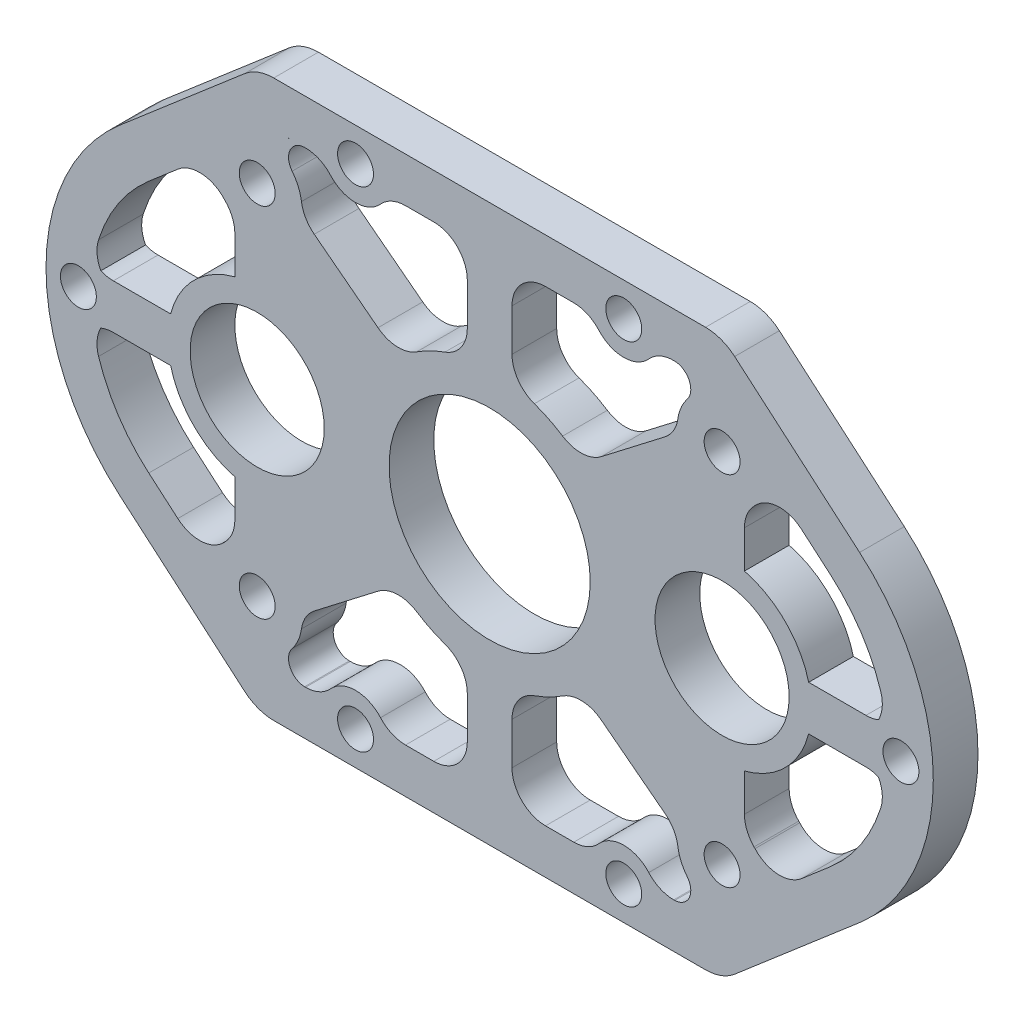
SolidWorks part; units mm, degrees
material "6061-T6 (SS)"
ref_plane "Front Plane" through (0, 0, 0) normal (0, 0, 1) x (1, 0, 0)
ref_plane "Top Plane" through (0, 0, 0) normal (0, 1, 0) x (1, 0, 0)
ref_plane "Right Plane" through (0, 0, 0) normal (1, 0, 0) x (0, 0, -1)
sketch "Sketch1" plane through (0, 0, 0) normal (0, 0, 1) x (1, 0, 0)
  line L0 (127, 25.4) -> (127, 0) construction
  line L1 (0, 0) -> (254, 0)
  line L2 (0, 0) -> (0, 25.4)
  line L3 (0, 25.4) -> (254, 25.4)
  line L4 (254, 0) -> (254, 25.4)
  line L18 (110.6338, 19.05) -> (106.9677, 12.7)
  line L19 (106.9677, 12.7) -> (110.6338, 6.35)
  line L20 (110.6338, 6.35) -> (117.9662, 6.35)
  line L21 (117.9662, 6.35) -> (121.6323, 12.7)
  line L22 (121.6323, 12.7) -> (117.9662, 19.05)
  line L23 (117.9662, 19.05) -> (110.6338, 19.05)
  circle A0 centre (81.28, 12.7) radius 30 construction
  circle A1 centre (147.32, 12.7) radius 30 construction
  circle A2 centre (81.28, 12.7) radius 7.62 construction
  circle A3 centre (147.32, 12.7) radius 8.636
  circle A4 centre (81.28, 12.7) radius 8.636
  circle A5 centre (147.32, 12.7) radius 7.62 construction
  circle A6 centre (114.3, 12.7) radius 25.4 construction
  circle A7 centre (114.3, 12.7) radius 26.67
  circle A8 centre (114.3, 12.7) radius 22.2377 construction
  circle A11 centre (114.3, 12.7) radius 6.35 construction
  point P14 (162.2423, 6.35)
  point P18 (165.1456, -9.525)
  point P19 (124.1885, 11.0952)
  point P20 (193.339, 12.7)
  point P21 (160.2579, 12.7)
  point P24 (158.7898, 12.7)
  point P25 (121.401, -22.0517)
  point P26 (113.0638, -6.35)
  point P27 (143.596, -12.7)
  point P28 (0, 0)
  point P29 (108.9412, 0)
  point P30 (0, 0)
  point P31 (132.7556, 0)
  point P32 (0, 0)
  point P33 (0, 0)
  point P34 (108.3304, -9.525)
  point P35 (166.067, 12.7)
  point P36 (170.1883, 18.3793)
  point P37 (118.8223, -1.6922)
  point P38 (145.9164, 0)
  point P39 (147.111, -5.8155)
  point P40 (0, 0)
  point P41 (83.1995, -20.6191)
  point P42 (82.353, -17.8742)
  point P43 (114.3, -9.525)
  point P44 (81.28, 12.7)
  point P45 (0, 0)
  point P46 (0, 12.7)
  point P47 (0, 0)
  point P48 (0, 0)
  point P49 (0, 0)
  dimension "D4" = 17.272
  dimension "D9" = 53.34
  dimension "D13" = 12.7
  dimension "D1" = 25.4
  dimension "D2" = 254
  dimension "D10" = 12.7
  dimension "D12" = 12.7
sketch "Sketch3" plane through (0, 0, 0) normal (0, 0, 1) x (1, 0, 0)
  line L0 (81.28, 42.7) -> (147.32, 42.7) construction
  line L5 (81.28, 12.7) -> (114.3, 12.7) construction
  line L6 (114.3, 12.7) -> (147.32, 12.7) construction
  line L9 (114.3, 42.7) -> (114.3, -17.3) construction
  line L10 (61.7477, 35.4704) -> (81.28, 52.225)
  line L25 (81.28, 52.225) -> (147.32, 52.225)
  line L26 (147.32, 52.225) -> (166.8523, 35.4704)
  line L27 (110.6338, 19.05) -> (106.9677, 12.7)
  line L28 (106.9677, 12.7) -> (110.6338, 6.35)
  line L29 (110.6338, 6.35) -> (117.9662, 6.35)
  line L30 (117.9662, 6.35) -> (121.6323, 12.7)
  line L31 (121.6323, 12.7) -> (117.9662, 19.05)
  line L32 (117.9662, 19.05) -> (110.6338, 19.05)
  line L33 (110.565, 18.9308) -> (106.9677, 12.7)
  line L34 (106.9677, 12.7) -> (110.6338, 6.35)
  line L35 (110.6338, 6.35) -> (117.9662, 6.35)
  line L36 (117.9662, 6.35) -> (121.6323, 12.7)
  line L37 (121.6323, 12.7) -> (117.9662, 19.05)
  line L38 (117.9662, 19.05) -> (110.6338, 19.05)
  line L39 (96.3395, 30.6605) -> (132.2605, -5.2605) construction
  line L40 (99.2405, 30.6605) -> (81.28, 12.7) construction
  line L41 (95.25, 47.4625) -> (133.35, 47.4625) construction
  line L42 (81.28, -17.3) -> (147.32, -17.3) construction
  line L43 (95.25, -22.0625) -> (133.35, -22.0625) construction
  line L44 (147.32, -26.825) -> (166.8523, -10.0704)
  line L45 (81.28, -26.825) -> (147.32, -26.825)
  line L46 (61.7477, -10.0704) -> (81.28, -26.825)
  line L47 (81.28, 12.7) -> (81.28, -12.7) construction
  line L48 (81.28, 12.7) -> (81.28, -12.7) construction
  line L49 (81.28, 12.7) -> (55.88, 12.7) construction
  circle A2 centre (81.28, 12.7) radius 30 construction
  circle A9 centre (114.3, 12.7) radius 26.67
  circle A10 centre (114.3, 12.7) radius 26.67 construction
  circle A11 centre (81.28, 12.7) radius 8.636
  circle A12 centre (81.28, 12.7) radius 8.636 construction
  circle A13 centre (147.32, 12.7) radius 8.636
  circle A16 centre (147.32, 12.7) radius 8.636 construction
  circle A17 centre (95.25, 47.4625) radius 2.5527
  circle A19 centre (114.3, 12.7) radius 25.4 construction
  circle A20 centre (114.3, 12.7) radius 22.2377 construction
  circle A22 centre (114.3, 12.7) radius 25.4 construction
  circle A23 centre (114.3, 12.7) radius 22.2377 construction
  arc A24 (108.3271, 25.6791) -> (108.3271, -0.2791) centre (81.28, 12.7) ccw
  circle A25 centre (114.3, 12.7) radius 14.2875
  circle A26 centre (81.28, 12.7) radius 9.525
  circle A27 centre (147.32, 12.7) radius 9.525
  circle A37 centre (133.35, 47.4625) radius 2.5527
  circle A38 centre (133.35, -22.0625) radius 2.5527
  circle A39 centre (95.25, -22.0625) radius 2.5527
  circle A40 centre (81.28, -12.7) radius 2.5527
  circle A41 centre (55.88, 12.7) radius 2.5527
  circle A42 centre (81.28, 38.1) radius 2.5527
  circle A43 centre (147.32, -12.7) radius 2.5527
  circle A44 centre (172.72, 12.7) radius 2.5527
  circle A45 centre (147.32, 38.1) radius 2.5527
  arc A47 (120.2729, -0.2791) -> (120.2729, 25.6791) centre (147.32, 12.7) ccw
  point P2 (114.3, 42.7)
  point P41 (114.3, 52.225)
  point P59 (114.3, 47.4625)
  point P69 (114.3, 12.7)
  point P78 (81.28, 12.7)
  point P84 (114.3, -22.0625)
  dimension "D3" = 45
  dimension "D4" = 9.525
  dimension "D2" = 45
  dimension "D8" = 25.4
  dimension "D14" = 28.575
  dimension "D15" = 19.05
  dimension "D16" = 3
  dimension "D5" = 5.1054
  dimension "D12" = 5.1054
  dimension "D7" = 4.7625
  dimension "D17" = 90
  dimension "2" = 50.8
  dimension "D6" = 19.05
  dimension "D9" = 0
  dimension "D10" = 0
  dimension "D11" = 0
  dimension "D13" = 0
extrude "Boss-Extrude1" add sketch "Sketch3" along normal blind 6.35 contours A24 A10 L26 L25 L10 A37 A17 | A24 L46 L45 L44 A10 A38 A39 | A10 A24 A12 A40 A42 | A23 A24 A25 | A23 A22 A12 | A22 A24 A10 A12 | A22 A12 A10 A24 | A24 A22 A23 | A24 A10 A22 | A22 A24 A23 | A25 A24 A23 | A25 A23 A24 | A24 A23 A22 | A24 A22 A10 | A23 A24 A22 | A23 A45 A25 A44 | A22 A45 A23 A44 A16 | A23 A45 A22 | A22 A45 A16 A10 | A10 A16 A43 | A22 A44 A23 | A22 A44 A10 A16 | A10 A26 A12 | A22 A12 A10 | A12 A22 | A10 A27 A16 | A16 A22 | A22 A16 A10 region at (81.1746, 41.9228, 0) region at (114.3, 45.5045, 0) region at (114.3, -20.1045, 0) region at (97.63, 12.7, 0) region at (114.3, 33.2042, 0) region at (114.3, -7.8042, 0) region at (147.4254, 41.9228, 0) region at (130.97, 12.7, 0)
fillet "Fillet2" radius 6.35 4 edges at (147.32, -26.825, 3.175) (81.28, -26.825, 3.175) (147.32, 52.225, 3.175) (81.28, 52.225, 3.175)
sketch "Sketch9" plane through (0, 0, 6.35) normal (0, 0, 1) x (1, 0, 0)
  line L0 (144.9696, -20.475) -> (162.7179, -5.2507)
  line L1 (162.7179, 30.6507) -> (144.9696, 45.875)
  line L2 (144.9696, 45.875) -> (83.6304, 45.875)
  line L3 (83.6304, 45.875) -> (65.8821, 30.6507)
  line L4 (65.8821, -5.2507) -> (83.6304, -20.475)
  line L5 (83.6304, -20.475) -> (144.9696, -20.475)
  line L6 (149.104, -25.2947) -> (166.8523, -10.0704)
  line L7 (166.8523, 35.4704) -> (149.104, 50.6947)
  line L8 (144.9696, 52.225) -> (83.6304, 52.225)
  line L9 (79.496, 50.6947) -> (61.7477, 35.4704)
  line L10 (61.7477, -10.0704) -> (79.496, -25.2947)
  line L11 (83.6304, -26.825) -> (144.9696, -26.825)
  line L12 (149.104, -25.2947) -> (166.8523, -10.0704)
  line L13 (166.8523, 35.4704) -> (149.104, 50.6947)
  line L14 (144.9696, 52.225) -> (83.6304, 52.225)
  line L15 (79.496, 50.6947) -> (61.7477, 35.4704)
  line L16 (61.7477, -10.0704) -> (79.496, -25.2947)
  line L17 (83.6304, -26.825) -> (144.9696, -26.825)
  line L18 (81.28, 38.1) -> (81.28, 12.7) construction
  line L19 (81.28, 12.7) -> (81.28, -12.7) construction
  line L20 (147.32, -12.7) -> (147.32, 12.7) construction
  line L21 (147.32, 12.7) -> (147.32, 38.1) construction
  line L22 (81.28, 12.7) -> (114.3, 12.7) construction
  line L23 (114.3, 12.7) -> (147.32, 12.7) construction
  line L24 (147.32, 12.7) -> (114.3, 12.7) construction
  line L25 (114.3, 12.7) -> (147.32, -12.7) construction
  line L26 (81.28, -12.7) -> (114.3, 12.7) construction
  line L27 (114.3, 12.7) -> (81.28, 38.1) construction
  line L28 (114.3, 12.7) -> (147.32, 38.1) construction
  line L29 (114.3, 12.7) -> (114.3, 45.875) construction
  line L30 (114.3, 12.7) -> (114.3, -20.475) construction
  line L31 (116.2358, 15.2166) -> (83.2158, 40.6166)
  line L32 (112.3642, 10.1834) -> (145.3842, -15.2166)
  line L33 (116.2358, 10.1834) -> (149.2558, 35.5834)
  line L34 (112.3642, 10.1834) -> (79.3442, 35.5834)
  line L35 (116.2358, 15.2166) -> (149.2558, -10.1834)
  line L36 (112.3642, 15.2166) -> (145.3842, 40.6166)
  line L37 (81.28, 12.7) -> (55.88, 12.7) construction
  line L38 (147.32, 12.7) -> (172.72, 12.7) construction
  line L39 (81.28, 9.525) -> (55.88, 9.525)
  line L40 (81.28, 9.525) -> (114.3, 9.525)
  line L41 (114.3, 9.525) -> (147.32, 9.525)
  line L42 (147.32, 9.525) -> (172.72, 9.525)
  line L43 (81.28, 15.875) -> (55.88, 15.875)
  line L44 (81.28, 15.875) -> (114.3, 15.875)
  line L45 (114.3, 15.875) -> (147.32, 15.875)
  line L46 (147.32, 15.875) -> (172.72, 15.875)
  line L47 (83.2158, -15.2166) -> (116.2358, 10.1834)
  line L48 (79.3442, -10.1834) -> (112.3642, 15.2166)
  line L49 (111.125, 12.7) -> (111.125, -20.475)
  line L50 (117.475, 12.7) -> (117.475, -20.475)
  line L51 (117.475, 12.7) -> (117.475, 45.875)
  line L52 (111.125, 12.7) -> (111.125, 45.875)
  line L53 (78.105, 38.1) -> (78.105, 12.7)
  line L54 (78.105, 12.7) -> (78.105, -12.7)
  line L55 (150.495, -12.7) -> (150.495, 12.7)
  line L56 (150.495, 12.7) -> (150.495, 38.1)
  line L57 (84.455, 38.1) -> (84.455, 12.7)
  line L58 (84.455, 12.7) -> (84.455, -12.7)
  line L59 (144.145, -12.7) -> (144.145, 12.7)
  line L60 (144.145, 12.7) -> (144.145, 38.1)
  circle A0 centre (55.88, 12.7) radius 4.6
  circle A1 centre (95.25, 47.4625) radius 4.7625
  arc A2 (166.8523, -10.0704) -> (166.8523, 35.4704) centre (147.32, 12.7) ccw
  arc A3 (61.7477, 35.4704) -> (61.7477, -10.0704) centre (81.28, 12.7) ccw
  arc A4 (166.8523, -10.0704) -> (166.8523, 35.4704) centre (147.32, 12.7) ccw
  arc A5 (61.7477, 35.4704) -> (61.7477, -10.0704) centre (81.28, 12.7) ccw
  circle A6 centre (133.35, 47.4625) radius 4.7625
  circle A7 centre (172.72, 12.7) radius 4.6
  circle A8 centre (133.35, -22.0625) radius 4.7625
  circle A9 centre (95.25, -22.0625) radius 4.7625
  circle A10 centre (81.28, 12.7) radius 9.525
  circle A11 centre (81.28, -12.7) radius 6.35
  circle A12 centre (81.28, 38.1) radius 6.35
  circle A13 centre (147.32, 38.1) radius 6.35
  circle A14 centre (147.32, 12.7) radius 9.525
  circle A15 centre (147.32, -12.7) radius 6.35
  arc A16 (144.9696, -26.825) -> (149.104, -25.2947) centre (144.9696, -20.475) ccw
  arc A17 (144.9696, -26.825) -> (149.104, -25.2947) centre (144.9696, -20.475) ccw
  arc A18 (149.104, 50.6947) -> (144.9696, 52.225) centre (144.9696, 45.875) ccw
  arc A19 (149.104, 50.6947) -> (144.9696, 52.225) centre (144.9696, 45.875) ccw
  arc A20 (83.6304, 52.225) -> (79.496, 50.6947) centre (83.6304, 45.875) ccw
  arc A21 (83.6304, 52.225) -> (79.496, 50.6947) centre (83.6304, 45.875) ccw
  arc A22 (79.496, -25.2947) -> (83.6304, -26.825) centre (83.6304, -20.475) ccw
  arc A23 (79.496, -25.2947) -> (83.6304, -26.825) centre (83.6304, -20.475) ccw
  arc A24 (162.7179, -5.2507) -> (162.7179, 30.6507) centre (147.32, 12.7) ccw
  arc A25 (144.9696, 45.875) -> (144.9696, 45.875) centre (144.9696, 45.875) ccw
  arc A26 (83.6304, 45.875) -> (83.6304, 45.875) centre (83.6304, 45.875) ccw
  arc A27 (65.8821, 30.6507) -> (65.8821, -5.2507) centre (81.28, 12.7) ccw
  arc A28 (83.6304, -20.475) -> (83.6304, -20.475) centre (83.6304, -20.475) ccw
  arc A29 (144.9696, -20.475) -> (144.9696, -20.475) centre (144.9696, -20.475) ccw
  circle A30 centre (114.3, 12.7) radius 19.05
  circle A32 centre (81.28, 12.7) radius 12.7
  circle A33 centre (147.32, 12.7) radius 12.7
  dimension "D2" = 19.05
  dimension "D3" = 12.7
  dimension "D4" = 38.1
  dimension "D18" = 25.4
  dimension "D17" = 6.35
  dimension "D1" = 0
  dimension "D5" = 3.175
  dimension "D6" = 3.175
  dimension "D7" = 3.175
  dimension "D8" = 3.175
  dimension "D9" = 3.175
  dimension "D10" = 3.175
  dimension "D11" = 3.175
  dimension "D12" = 3.175
  dimension "D13" = 3.175
  dimension "D14" = 3.175
  dimension "D15" = 3.175
  dimension "D16" = 3.175
extrude "Cut-Extrude2" cut sketch "Sketch9" against normal blind 6.35 contours A32 L53 A12 L3 A27 A0 L43 | A32 L39 A0 A27 L4 A11 L54 | A30 L52 L2 A1 L3 A12 L31 | A30 L36 A13 L1 L2 A6 L51 | A33 L46 A7 A24 L1 A13 L56 | A33 L55 A15 L0 A24 A7 L42 | A30 L50 L5 A8 L0 A15 L32 | A30 L47 A11 L4 L5 A9 L49 region at (128.7733, -12.6609, 6.35) region at (159.8487, -0.042, 6.35) region at (99.8267, -12.6609, 6.35) region at (159.8487, 25.442, 6.35) region at (68.7513, -0.042, 6.35) region at (128.7733, 38.0609, 6.35) region at (68.7513, 25.442, 6.35) region at (99.8267, 38.0609, 6.35)
fillet "Fillet3" radius 4.7625 48 edges at (117.475, 45.875, 3.175) (128.8599, 45.875, 3.175) (137.8401, 45.875, 3.175) (144.9696, 45.875, 3.175) (146.6698, 44.4166, 3.175) (141.0253, 37.2636, 3.175) (127.2525, 26.6691, 3.175) (117.475, 31.4836, 3.175) (101.3475, 26.6691, 3.175) (81.9302, 44.4166, 3.175) (83.6304, 45.875, 3.175) (90.7599, 45.875, 3.175) (99.7401, 45.875, 3.175) (111.125, 45.875, 3.175) (111.125, 31.4836, 3.175) (87.5747, 37.2636, 3.175) (111.125, -6.0836, 3.175) (111.125, -20.475, 3.175) (99.7401, -20.475, 3.175) (90.7599, -20.475, 3.175) (81.9302, -19.0166, 3.175) (87.5747, -11.8636, 3.175) (101.3475, -1.2691, 3.175) (83.6304, -20.475, 3.175) (127.2525, -1.2691, 3.175) (141.0253, -11.8636, 3.175) (146.6698, -19.0166, 3.175) (144.9696, -20.475, 3.175) (137.8401, -20.475, 3.175) (128.8599, -20.475, 3.175) (117.475, -6.0836, 3.175) (117.475, -20.475, 3.175) (169.3914, 15.875, 3.175) (150.495, 32.6007, 3.175) (153.662, 38.4188, 3.175) (170.6137, 16.7895, 3.175) (78.105, 32.6007, 3.175) (59.2086, 15.875, 3.175) (74.938, 38.4188, 3.175) (57.9863, 16.7895, 3.175) (78.105, -7.2007, 3.175) (74.938, -13.0188, 3.175) (57.9863, 8.6105, 3.175) (59.2086, 9.525, 3.175) (150.495, -7.2007, 3.175) (153.662, -13.0188, 3.175) (169.3914, 9.525, 3.175) (170.6137, 8.6105, 3.175)
sketch "Sketch11" plane through (0, 0, 6.35) normal (0, 0, 1) x (1, 0, 0)
  line L4 (53.3273, 12.7) -> (175.2727, 12.7) construction
  line L5 (114.3, 52.225) -> (114.3, -26.825) construction
  line L6 (83.6304, 52.225) -> (144.9696, 52.225) construction
  line L7 (83.6304, -26.825) -> (144.9696, -26.825) construction
  line L16 (143.3237, -20.4736) -> (140.4495, -20.475)
  line L17 (143.3237, 45.8736) -> (140.4495, 45.875)
  line L18 (85.2763, 45.8736) -> (88.1505, 45.875)
  line L19 (85.3931, -20.475) -> (88.1505, -20.475) construction
  line L20 (85.3931, -20.475) -> (88.1505, -20.475)
  circle A1 centre (55.88, 12.7) radius 2.5527 construction
  circle A3 centre (172.72, 12.7) radius 2.5527 construction
  arc A17 (86.2424, -16.662) -> (88.1505, -20.475) centre (88.0778, -18.1274) ccw
  arc A18 (86.2424, -16.662) -> (87.568, -13.5855) centre (81.28, -12.7) ccw construction
  arc A19 (86.2424, -16.662) -> (85.2763, -20.4736) centre (89.9642, -19.6335) ccw construction
  arc A21 (142.3576, -16.662) -> (143.3237, -20.4736) centre (138.6358, -19.6335) cw
  arc A22 (142.3576, -16.662) -> (140.4495, -20.475) centre (140.5222, -18.1274) cw
  arc A23 (142.3576, 42.062) -> (140.4495, 45.875) centre (140.5222, 43.5274) ccw
  arc A24 (142.3576, 42.062) -> (143.3237, 45.8736) centre (138.6358, 45.0335) ccw
  arc A25 (86.2424, 42.062) -> (85.2763, 45.8736) centre (89.9642, 45.0335) cw
  arc A26 (86.2424, 42.062) -> (88.1505, 45.875) centre (88.0778, 43.5274) cw
  arc A27 (85.2763, -20.4736) -> (85.3931, -20.475) centre (85.3931, -15.7125) ccw construction
  arc A28 (85.2763, -20.4736) -> (85.3931, -20.475) centre (85.3931, -15.7125) ccw
  arc A29 (86.2424, -16.662) -> (85.2763, -20.4736) centre (89.9642, -19.6335) ccw
  point P3 (0, 0)
  point P4 (0, 0)
  point P5 (0, 0)
  point P11 (0, 0)
  point P19 (85.8194, -17.2877)
  point P21 (87.9183, -20.475)
  point P28 (0, 0)
  point P29 (86.6216, -20.475)
  point P31 (0, 0)
  point P32 (88.0778, -20.475)
  point P49 (0, 0)
  point P54 (85.1281, -20.4736)
  point P56 (85.3102, -20.4736)
extrude "Boss-Extrude3" add sketch "Sketch11" against normal up to surface (6.35 mm away) contours A17 A29 A28 L20 | A21 A22 L16 | A25 A26 L18 | A23 A24 L17 | L17 A23 A24 region at (142.7262, -19.5499, 6.35) region at (142.7262, 44.9499, 6.35) region at (85.8738, 44.9499, 6.35) region at (85.8741, -19.5506, 6.35) up to face at (96.993, 39.8725, 0)
equation "\"NEO\"= 60mm"
equation "\"D3@Sketch1\"=\"NEO\""
equation "\"D5@Sketch1\"=\"NEO\""
